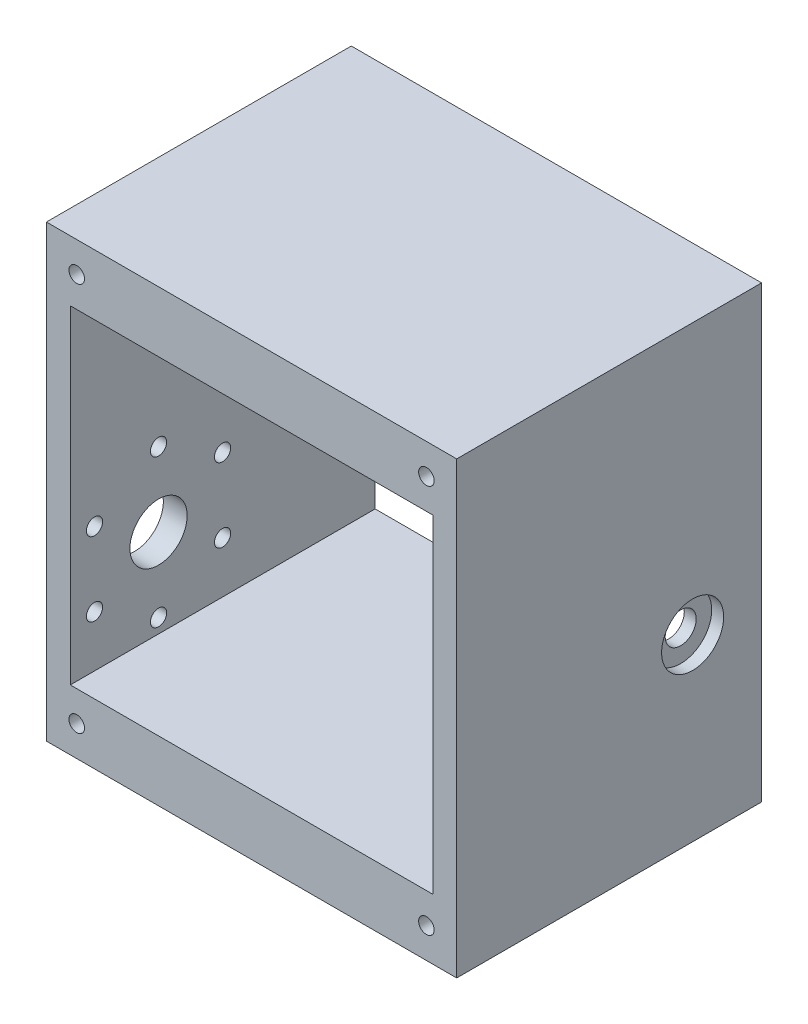
SolidWorks part; units mm, degrees
ref_plane "Front Plane" through (0, 0, 0) normal (0, 0, 1) x (1, 0, 0)
ref_plane "Top Plane" through (0, 0, 0) normal (0, 1, 0) x (1, 0, 0)
ref_plane "Right Plane" through (0, 0, 0) normal (1, 0, 0) x (0, 0, -1)
sketch "Sketch1" plane through (0, 0, 0) normal (0, 0, 1) x (1, 0, 0)
  line L1 (-43, -47.117) -> (43, -47.117)
  line L2 (-43, -47.117) -> (-43, 47.117)
  line L3 (-43, 47.117) -> (43, 47.117)
  line L4 (43, -47.117) -> (43, 47.117)
  line L5 (-43, -47.117) -> (43, 47.117) construction
  line L6 (-43, 47.117) -> (43, -47.117) construction
  point P0 (0, 0)
  dimension "D1" = 86
  dimension "D2" = 94.234
extrude "Boss-Extrude1" add sketch "Sketch1" along normal blind 63.9031
sketch "Sketch2" plane through (0, 0, 63.9031) normal (0, 0, 1) x (1, 0, 0)
  line L0 (-43, 47.117) -> (-43, -47.117) construction
  line L1 (-38, -34.417) -> (38, -34.417)
  line L2 (-38, -34.417) -> (-38, 34.417)
  line L3 (-38, 34.417) -> (38, 34.417)
  line L4 (38, -34.417) -> (38, 34.417)
  line L5 (-38, -34.417) -> (38, 34.417) construction
  line L6 (-38, 34.417) -> (38, -34.417) construction
  line L7 (43, 47.117) -> (-43, 47.117) construction
  point P0 (0, 0)
  dimension "D1" = 5
  dimension "D2" = 12.7
extrude "Cut-Extrude1" cut sketch "Sketch2" against normal through all
hole_wizard "Ø6.5 (6.5) Diameter Hole1" positions "Sketch3" profile "Sketch4" hole size "Ø6.5" standard "ANSI Metric" end condition up to next
sketch "Sketch3" plane through (43, 0, 0) normal (1, 0, 0) x (0, 0, -1)
  line L0 (0, -47.117) -> (0, 47.117) construction
  line L1 (0, 34.417) -> (-63.9031, 34.417) construction
  point P0 (-14.4502, -9.525)
  dimension "D1" = 14.4502
  dimension "D2" = 43.942
sketch "Sketch4" plane through (43, -9.525, 14.4502) normal (0, 1, 0) x (0, 0, -1)
  line L0 (0, 0) -> (0, 5)
  line L1 (0, 5) -> (3.25, 5)
  line L2 (3.25, 5) -> (3.25, 0)
  line L5 (3.25, 0) -> (0, 0)
  line L11 (0, -6.35) -> (0, 107.95) construction
  dimension "Thru Hole Dia." = 6.5
  dimension "Thru Hole Depth" = 5
sketch "Sketch5" plane through (-43, 0, 0) normal (-1, 0, 0) x (0, 0, 1)
  line L0 (63.9031, 47.117) -> (63.9031, -47.117) construction
  line L1 (0, -34.417) -> (63.9031, -34.417) construction
  point P0 (45.4031, -15.917)
  dimension "D1" = 18.5
  dimension "D2" = 18.5
hole_wizard "Ø12.0 (12) Diameter Hole1" positions "Sketch6" profile "Sketch7" hole size "Ø12.0" standard "ANSI Metric" end condition up to next
sketch "Sketch6" plane through (-43, 0, 0) normal (-1, 0, 0) x (0, 0, 1)
  point P0 (45.4031, -15.917)
sketch "Sketch7" plane through (-43, -15.917, 45.4031) normal (0, 1, 0) x (0, 0, 1)
  line L0 (0, 0) -> (0, 5)
  line L1 (0, 5) -> (6, 5)
  line L2 (6, 5) -> (6, 0)
  line L5 (6, 0) -> (0, 0)
  line L11 (0, -6.35) -> (0, 107.95) construction
  dimension "Thru Hole Dia." = 12
  dimension "Thru Hole Depth" = 5
hole_wizard "CSK for M3 Flat Head Machine Screw1" positions "Sketch8" profile "Sketch9" countersink size "M3" standard "ANSI Metric" end condition up to next
sketch "Sketch8" plane through (-43, 0, 0) normal (-1, 0, 0) x (0, 0, 1)
  line L0 (45.4031, -15.917) -> (45.4031, -0.417) construction
  point P0 (45.4031, -0.417)
  point P12 (58.8265, -8.167)
  point P13 (58.8265, -23.667)
  point P14 (45.4031, -31.417)
  point P15 (31.9797, -23.667)
  point P16 (31.9797, -8.167)
  dimension "D2" = 15.5
sketch "Sketch9" plane through (-43, -0.417, 45.4031) normal (0, 1, 0) x (0, 0, 1)
  line L0 (0, 0) -> (0, 5)
  line L1 (0, 5) -> (1.7, 5)
  line L2 (1.7, 5) -> (1.7, 1.45)
  line L3 (1.7, 1.45) -> (3.15, 0)
  line L5 (3.15, 0) -> (0, 0)
  line L6 (-1.7, 1.45) -> (-3.15, 0) construction
  line L11 (0, -6.35) -> (0, 107.95) construction
  dimension "Thru Hole Dia." = 3.4
  dimension "Thru Hole Depth" = 5
  dimension "Near C'Sink Dia." = 6.3
  dimension "Near C'Sink Angle" = 90
hole_wizard "#4 Clearance Hole1" positions "Sketch10" profile "Sketch11" hole size "#4" standard "ANSI Inch" end condition through all
sketch "Sketch10" plane through (0, 0, 63.9031) normal (0, 0, 1) x (1, 0, 0)
  line L0 (-43, 47.117) -> (-43, -47.117) construction
  line L1 (43, 47.117) -> (-43, 47.117) construction
  line L2 (43, -47.117) -> (43, 47.117) construction
  line L3 (-43, -47.117) -> (43, -47.117) construction
  point P0 (-36.65, 40.767)
  point P2 (36.65, 40.767)
  point P4 (-36.65, -40.767)
  point P6 (36.65, -40.767)
  dimension "D1" = 6.35
  dimension "D2" = 6.35
  dimension "D3" = 6.35
  dimension "D4" = 6.35
sketch "Sketch11" plane through (-36.65, 40.767, 63.9031) normal (1, 0, 0) x (0, -1, 0)
  line L0 (0, 0) -> (0, 63.9031)
  line L1 (0, 63.9031) -> (1.6319, 63.9031)
  line L2 (1.6319, 63.9031) -> (1.6319, 0)
  line L5 (1.6319, 0) -> (0, 0)
  line L11 (0, -6.35) -> (0, 107.95) construction
  dimension "Thru Hole Dia." = 3.2639
  dimension "Thru Hole Depth" = 63.9031
sketch "Sketch12" plane through (43, 0, 0) normal (1, 0, 0) x (0, 0, -1)
  circle A0 centre (-14.4502, -9.525) radius 6.5
  dimension "D1" = 13
extrude "Cut-Extrude2" cut sketch "Sketch12" against normal blind 2.5
equation "\"PCB Width\"= 1940mil"
equation "\"PCB Height\"= 2210mil"
equation "\"PCB Thickness\"= 63mil"
equation "\"PCB Mount Height\"= 0.25in"
equation "\"Motor Body Front Diameter\"= 37mm"
equation "\"Motor Body Front Length\"= 30mm"
equation "\"Motor Bearing Length\"= 5mm"
equation "\"Motor Body Back Length\"= 33.3mm"
equation "\"Motor PCR\"= 31mm / 2"
equation "\"Large PVC Fittings Wall Thickness\"= 15in / 64"
equation "\"Large PVC Pipe Outer Diameter\"= 3.5in"
equation "\"Box Width\"= 2 * \"Motor Bearing Length\" + \"Motor Body Front Length\" + \"Motor Body Back Length\" + 0.5in"
equation "\"Box Hole Center to Edge Distance\"= 250mil"
equation "\"Box Ceiling and Floor Thickness\"= 2 * \"Box Hole Center to Edge Distance\""
equation "\"Box Height\"= 2 * \"Box Ceiling and Floor Thickness\" + \"PCB Height\" + 0.5in"
equation "\"Box Middle Depth\"= \"Large PVC Fittings Wall Thickness\" + \"Large PVC Pipe Outer Diameter\" / 2 + \"Motor Body Front Diameter\" / 2 - \"Motor Bearing Length\""
equation "\"D1@Sketch1\"=\"Box Width\""
equation "\"D2@Sketch1\"=\"Box Height\""
equation "\"D1@Boss-Extrude1\"=\"Box Middle Depth\" "
equation "\"D1@Sketch2\"=\"Motor Bearing Length\""
equation "\"D2@Sketch2\"=\"Box Ceiling and Floor Thickness\""
equation "\"D1@Sketch3\"=\"PCB Mount Height\" + \"PCB Thickness\" + 6.5mm"
equation "\"D2@Sketch3\"=\"PCB Height\" - 0.48in"
equation "\"Motor Body Front Radius\"= \"Motor Body Front Diameter\" / 2"
equation "\"D1@Sketch5\"=\"Motor Body Front Radius\""
equation "\"D2@Sketch5\"=\"Motor Body Front Radius\""
equation "\"D2@Sketch8\"=\"Motor PCR\""
equation "\"D1@Sketch10\"=\"Box Hole Center to Edge Distance\""
equation "\"D2@Sketch10\"=\"Box Hole Center to Edge Distance\""
equation "\"D3@Sketch10\"=\"Box Hole Center to Edge Distance\""
equation "\"D4@Sketch10\"=\"Box Hole Center to Edge Distance\""
equation "\"D1@Sketch12\"=13mm"
equation "\"D1@Cut-Extrude2\"=\"Motor Bearing Length\" / 2"
